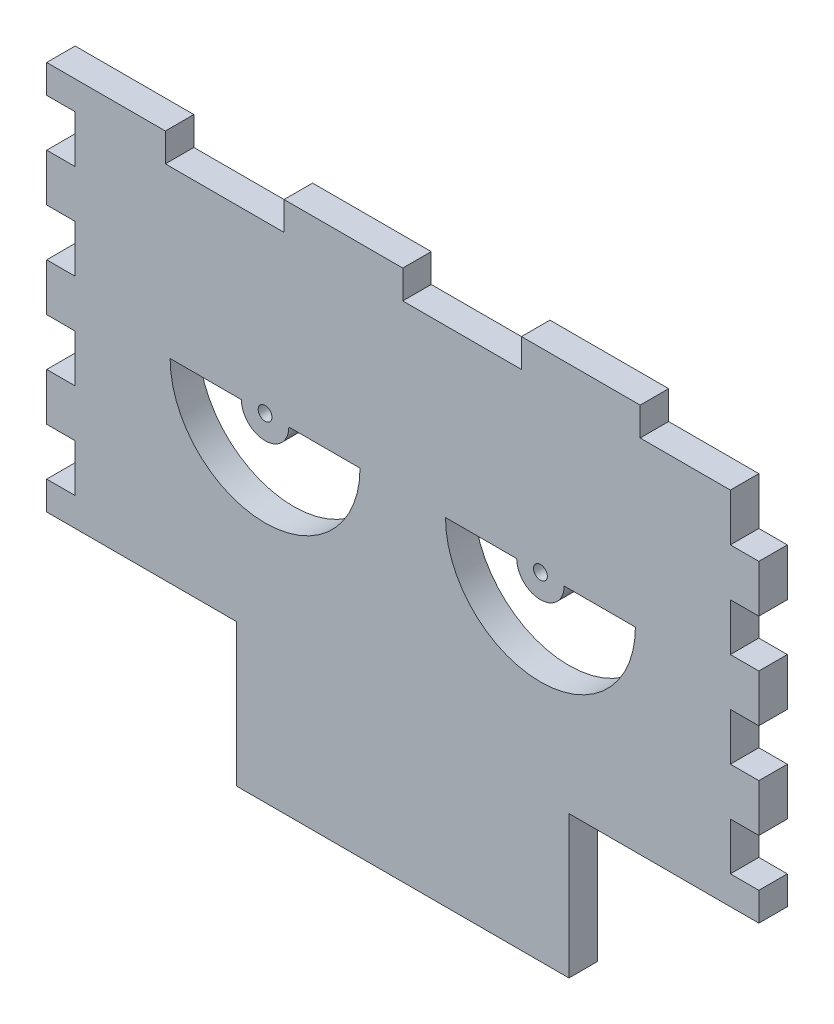
SolidWorks part; units mm, degrees
material "Pine"
ref_plane "Front Plane" through (0, 0, 0) normal (0, 0, 1) x (1, 0, 0)
ref_plane "Top Plane" through (0, 0, 0) normal (0, 1, 0) x (1, 0, 0)
ref_plane "Right Plane" through (0, 0, 0) normal (1, 0, 0) x (0, 0, -1)
sketch "Sketch1" plane through (0, 0, 0) normal (0, 0, 1) x (1, 0, 0)
  line L1 (75, -41) -> (-75, -41)
  line L2 (75, -41) -> (75, 41)
  line L3 (75, 41) -> (-75, 41)
  line L4 (-75, -41) -> (-75, 41)
  line L5 (75, -41) -> (-75, 41) construction
  line L6 (75, 41) -> (-75, -41) construction
  line L7 (-35, -41) -> (35, -41)
  line L8 (-35, -41) -> (-35, -71)
  line L9 (-35, -71) -> (35, -71)
  line L10 (35, -41) -> (35, -71)
  point P0 (0, 0)
  point P10 (0, -71)
  dimension "D1" = 150
  dimension "D2" = 82
  dimension "D3" = 30
  dimension "D4" = 70
  dimension "D5" = 0
extrude "Boss-Extrude1" add sketch "Sketch1" along normal blind 6 contours L10 L1 L8 L9 | L4 L1 L2 L3 region at (0, 0, 0) region at (0, -56, 0)
sketch "Sketch2" plane through (0, 0, 6) normal (0, 0, 1) x (1, 0, 0)
  line L0 (-75, -41) -> (-75, 41) construction
  line L1 (-75, 35) -> (-69, 35)
  line L2 (-75, 35) -> (-75, 25)
  line L3 (-75, 25) -> (-69, 25)
  line L4 (-69, 35) -> (-69, 25)
  line L5 (75, 41) -> (-75, 41) construction
  line L6 (69, 35) -> (69, 25)
  line L7 (69, 35) -> (75, 35)
  line L8 (75, 35) -> (75, 25)
  line L9 (69, 25) -> (75, 25)
  line L10 (69, 15) -> (69, 5)
  line L11 (69, 15) -> (75, 15)
  line L12 (75, 15) -> (75, 5)
  line L13 (69, 5) -> (75, 5)
  line L14 (-75, 15) -> (-75, 5)
  line L15 (-75, 15) -> (-69, 15)
  line L16 (-69, 15) -> (-69, 5)
  line L17 (-75, 5) -> (-69, 5)
  line L18 (-75, -5) -> (-75, -15)
  line L19 (-75, -5) -> (-69, -5)
  line L20 (-69, -5) -> (-69, -15)
  line L21 (-75, -15) -> (-69, -15)
  line L22 (69, -5) -> (69, -15)
  line L23 (69, -5) -> (75, -5)
  line L24 (75, -5) -> (75, -15)
  line L25 (69, -15) -> (75, -15)
  line L26 (-75, -25) -> (-75, -35)
  line L27 (-75, -25) -> (-69, -25)
  line L28 (-69, -25) -> (-69, -35)
  line L29 (-75, -35) -> (-69, -35)
  line L30 (69, -25) -> (69, -35)
  line L31 (69, -25) -> (75, -25)
  line L32 (75, -25) -> (75, -35)
  line L33 (69, -35) -> (75, -35)
  dimension "D1" = 6
  dimension "D2" = 10
  dimension "D3" = 6
  dimension "D4" = 2
  dimension "D5" = 4
extrude "Cut-Extrude1" cut sketch "Sketch2" against normal blind 10
sketch "Sketch3" plane through (0, 0, 6) normal (0, 0, 1) x (1, 0, 0)
  line L24 (-49, 0) -> (-34, 0)
  line L25 (-9, 0) -> (-24, 0)
  line L26 (0, -3.3) -> (0, 3.3) construction
  line L27 (49, 0) -> (34, 0)
  line L28 (9, 0) -> (24, 0)
  circle A0 centre (-29, 0) radius 1.45
  arc A2 (-49, 0) -> (-9, 0) centre (-29, 0) ccw
  arc A3 (-34, 0) -> (-24, 0) centre (-29, 0) ccw
  circle A4 centre (29, 0) radius 1.45
  arc A5 (49, 0) -> (9, 0) centre (29, 0) cw
  arc A6 (34, 0) -> (24, 0) centre (29, 0) cw
  dimension "D2" = 2.9
  dimension "D3" = 20
  dimension "D1" = 29
  dimension "D5" = 180
  dimension "D4" = 15
extrude "Cut-Extrude2" cut sketch "Sketch3" against normal blind 6
sketch "Sketch4" plane through (0, 0, 6) normal (0, 0, 1) x (1, 0, 0)
  line L0 (25, 41) -> (25, 35)
  line L1 (75, 41) -> (50, 41)
  line L2 (75, 41) -> (75, 35)
  line L3 (75, 35) -> (50, 35)
  line L4 (50, 41) -> (50, 35)
  line L5 (25, 41) -> (0, 41)
  line L6 (0, 41) -> (0, 35)
  line L7 (25, 35) -> (0, 35)
  line L8 (-25, 41) -> (-25, 35)
  line L9 (-25, 41) -> (-50, 41)
  line L10 (-50, 41) -> (-50, 35)
  line L11 (-25, 35) -> (-50, 35)
  dimension "D1" = 25
  dimension "D2" = 6
  dimension "D3" = 3
extrude "Cut-Extrude3" cut sketch "Sketch4" against normal blind 6
